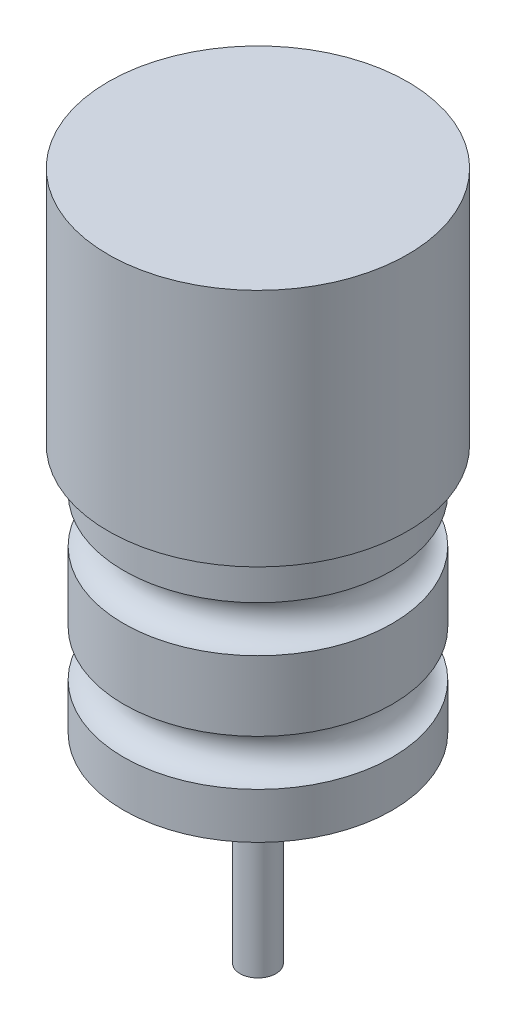
SolidWorks part; units mm, degrees
ref_plane "Plan de face" through (0, 0, 0) normal (0, 0, 1) x (1, 0, 0)
ref_plane "Plan de dessus" through (0, 0, 0) normal (0, 1, 0) x (1, 0, 0)
ref_plane "Plan de droite" through (0, 0, 0) normal (1, 0, 0) x (0, 0, -1)
sketch "Esquisse3" plane through (0, 0, 0) normal (0, 0, 1) x (1, 0, 0)
  line L0 (0, 0) -> (0, 83.371) construction
  line L1 (0, -20) -> (1.8, -20)
  line L2 (1.8, -20) -> (1.8, 0)
  line L3 (1.8, 0) -> (13.45, 0)
  line L4 (13.45, 0) -> (13.45, 4.6)
  line L5 (13.45, 4.6) -> (13.45, 9.2) construction
  line L6 (13.45, 9.2) -> (13.45, 16.2)
  line L7 (13.45, 16.2) -> (13.45, 20.8) construction
  line L8 (13.45, 20.8) -> (13.45, 25)
  line L9 (13.45, 25) -> (15, 25)
  line L10 (15, 25) -> (15, 49)
  line L11 (15, 49) -> (0, 49)
  line L12 (0, 49) -> (0, 0)
  line L13 (0, 0) -> (0, -20)
  line L14 (11.4879, 19.7) -> (11.4879, 5.7) construction
  arc A0 (13.45, 4.6) -> (13.45, 9.2) centre (13.45, 6.9) cw
  arc A1 (13.45, 16.2) -> (13.45, 20.8) centre (13.45, 18.5) cw
  dimension "D1" = 25
  dimension "D2" = 24
  dimension "D3" = 15
  dimension "D4" = 13.45
  dimension "D5" = 4.6
  dimension "D6" = 7
  dimension "D7" = 4.2
  dimension "D8" = 1.8
  dimension "D9" = 20
  dimension "D10" = 14
  dimension "D11" = 11.4879
revolve "Révolution1" add sketch "Esquisse3" angle 360 about L12
